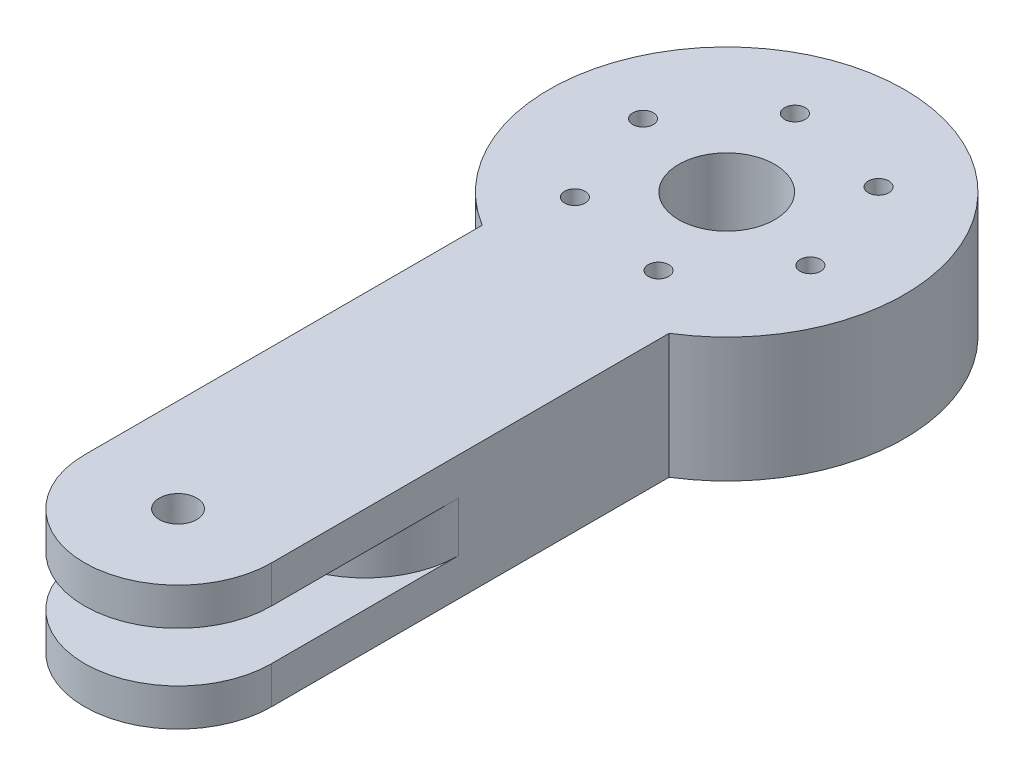
SolidWorks part; units mm, degrees
ref_plane "前视基准面" through (0, 0, 0) normal (0, 0, 1) x (1, 0, 0)
ref_plane "上视基准面" through (0, 0, 0) normal (0, 1, 0) x (1, 0, 0)
ref_plane "右视基准面" through (0, 0, 0) normal (1, 0, 0) x (0, 0, -1)
other "Configuration Table"
sketch "草图2" plane through (0, 10, 0) normal (0, 1, 0) x (0, 0, -1)
  circle A0 centre (-10.8245, 40.1252) radius 28.5
  circle A1 centre (-23.7168, 51.586) radius 1.65
  circle A2 centre (-7.3453, 57.0207) radius 1.65
  circle A3 centre (5.5471, 45.5599) radius 1.65
  circle A5 centre (2.0679, 28.6644) radius 1.65
  circle A6 centre (-27.196, 34.6905) radius 1.65
  circle A7 centre (-14.3036, 23.2297) radius 1.65
  circle A8 centre (-27.196, 34.6905) radius 1.65
  circle A9 centre (-10.8245, 40.1252) radius 7.7
extrude "凸台-拉伸2" add sketch "草图2" along normal blind 20 contours A0 A9 A7 A6 A5 A3 A2 A1 region at (-40.1252, 10, 38.5184)
sketch "草图3" plane through (0, 30, 0) normal (0, 1, 0) x (1, 0, 0)
  line L0 (-40.1252, -10.8245) -> (-40.1252, -98.8245)
  line L1 (-55.1252, -98.8245) -> (-55.1252, -35.0577)
  line L2 (-25.1252, -98.8245) -> (-25.1252, -35.0577)
  line L3 (-25.1252, -35.0577) -> (-25.1252, -35.0209)
  line L4 (-55.1252, -35.0577) -> (-55.1252, -35.0226)
  circle A0 centre (-40.1252, -98.8245) radius 15
  circle A1 centre (-40.1252, -10.8245) radius 28.5 construction
  circle M9 centre (-40.1252, -10.8245) radius 28.5
extrude "凸台-拉伸3" add sketch "草图3" against normal blind 6 contours A0 L2 L0 M9 | A0 L0 L1 M9 | A0 region at (-32.2463, 30, 62.5937) region at (-48.0041, 30, 62.5937) region at (-29.8186, 30, 88.5179)
sketch "草图5" plane through (0, 24, 0) normal (0, -1, 0) x (-1, 0, 0)
  line L0 (55.1252, -98.8245) -> (55.1252, -35.0577)
  line L1 (25.1252, -35.0577) -> (25.1252, -98.8245)
  line L2 (40.1252, -98.8242) -> (40.1252, -68.8242) construction
  line L3 (55.1252, -35.0577) -> (25.1252, -35.0577)
  line L4 (55.1252, -35.0577) -> (55.1252, -74.2958)
  line L5 (55.1252, -74.2958) -> (25.1252, -74.2958)
  line L6 (25.1252, -35.0577) -> (25.1252, -74.2958)
  circle A0 centre (40.1252, -98.8242) radius 15
  circle A1 centre (40.1252, -68.8242) radius 15
  arc M3 (55.1252, -35.0577) -> (25.1252, -35.0577) centre (40.1252, -10.8245) cw
  line M4 (25.1252, -35.0577) -> (25.1252, -98.8245)
  dimension "D1" = 63.7668
extrude "凸台-拉伸4" add sketch "草图5" along normal blind 8 contours L2 A1 L5 | A1 L2 L5 | A1 L5 | A1 L4 M3 M4 region at (-34.563, 24, 78.2347) region at (-45.6874, 24, 78.2347) region at (-40.1252, 24, 47.7476) region at (-40.1252, 24, 65.2898)
sketch "草图6" plane through (0, 16, 0) normal (0, -1, 0) x (-1, 0, 0)
  line L5 (55.1252, -35.0577) -> (25.1252, -35.0577)
  line L6 (55.1252, -35.0577) -> (55.1252, -98.8245)
  line L7 (55.1252, -98.8245) -> (25.1252, -98.8245)
  line L8 (25.1252, -35.0577) -> (25.1252, -98.8245)
  circle A0 centre (40.1252, -98.8245) radius 15
  line M1 (25.1252, -35.0577) -> (25.1252, -68.8242)
  arc M2 (25.1252, -68.8242) -> (55.1252, -68.8242) centre (40.1252, -68.8242) ccw
  line M3 (55.1252, -68.8242) -> (55.1252, -35.0577)
  arc M4 (55.1252, -35.0577) -> (25.1252, -35.0577) centre (40.1252, -10.8245) cw
extrude "凸台-拉伸5" add sketch "草图6" along normal blind 6 contours L7 A0 | L7 A0 | A0 L6 L8 M2 | M4 M1 M2 M3 region at (-40.1252, 16, 59.3893) region at (-40.1252, 16, 83.8243) region at (-40.1252, 16, 105.1907) region at (-40.1252, 16, 92.4583)
sketch "草图7" plane through (0, 10, 0) normal (0, -1, 0) x (-1, 0, 0)
  line L1 (85.1263, -162.5877) -> (25.1252, -162.5877)
  line L2 (85.1263, -162.5877) -> (85.1263, -35.0577)
  line L3 (85.1263, -35.0577) -> (25.1252, -35.0577)
  line L4 (25.1252, -162.5877) -> (25.1252, -35.0577)
  line L5 (55.1257, -35.0577) -> (55.1257, -162.5877) construction
  line L6 (85.1263, -98.8227) -> (25.1252, -98.8227) construction
  circle A0 centre (40.1257, -98.8227) radius 15
  circle A1 centre (40.1257, -98.8227) radius 3
  point P3 (55.1257, -98.8227)
  dimension "D1" = 6
extrude "切除-拉伸4" cut sketch "草图7" against normal blind 20 contours A1 region at (-40.1257, 10, 98.8227)
